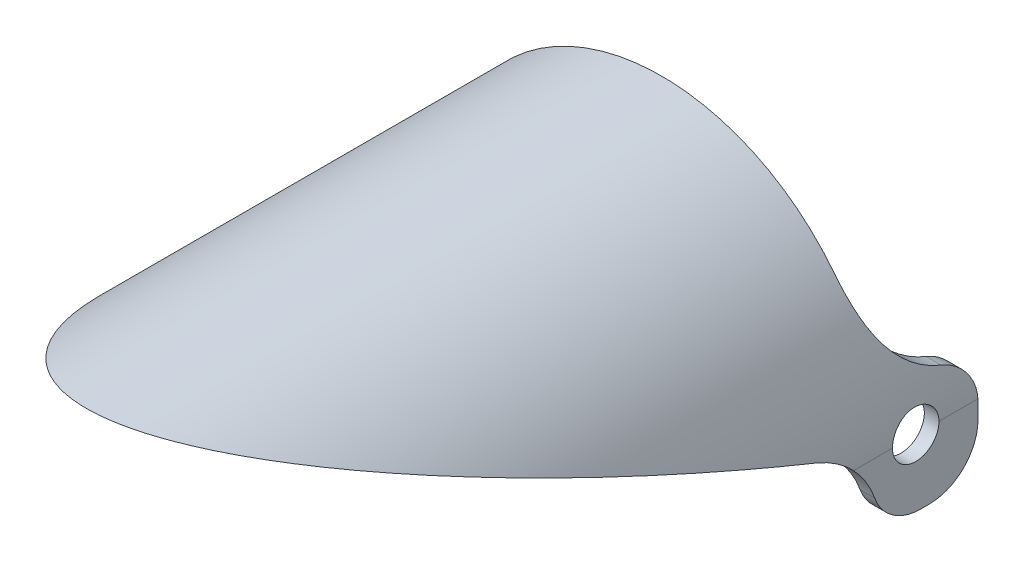
SolidWorks part; units mm, degrees
ref_plane "Front Plane" through (0, 0, 0) normal (0, 0, 1) x (1, 0, 0)
ref_plane "Top Plane" through (0, 0, 0) normal (0, 1, 0) x (1, 0, 0)
ref_plane "Right Plane" through (0, 0, 0) normal (1, 0, 0) x (0, 0, -1)
sketch "Sketch2" plane through (0, 0, 0) normal (0, 0, 1) x (1, 0, 0)
  line L0 (-44.875, 0) -> (-44.875, -13.7113)
  line L1 (-44.875, -13.7113) -> (-41.875, -13.7113)
  line L2 (44.875, -13.7113) -> (44.875, 0)
  line L3 (-41.875, 0) -> (-41.875, -13.7113)
  line L4 (41.875, 0) -> (41.875, -13.7113)
  line L5 (41.875, -13.7113) -> (44.875, -13.7113)
  arc A0 (44.875, 0) -> (-44.875, 0) centre (0, 0) ccw
  arc A1 (41.875, 0) -> (-41.875, 0) centre (0, 0) ccw
  circle A3 centre (0, 0) radius 41.875 construction
  circle A4 centre (0, 0) radius 44.875 construction
  point P4 (42.9142, 13.1202)
  point P13 (41.875, 0)
  dimension "D1" = 89.75
  dimension "D2" = 3
extrude "Boss-Extrude1" add sketch "Sketch2" along normal blind 138
sketch "Sketch3" plane through (0, 0, 0) normal (1, 0, 0) x (0, 0, -1)
  line L0 (-20, 44.875) -> (-20, 7.7299)
  line L1 (0, 44.875) -> (-138, 44.875) construction
  line L2 (-20, 7.7299) -> (0, 7.7299)
  line L3 (0, 0) -> (0, 44.875) construction
  line L4 (0, 7.7299) -> (0, -13.7113)
  line L5 (0, -13.7113) -> (-20, -13.7113)
  line L7 (-138, -13.7113) -> (0, -13.7113) construction
  line L8 (-20, -13.7113) -> (-20, 0)
  line L10 (-138, 0) -> (0, 0) construction
  line L11 (-138, 44.875) -> (-20, 44.875)
  line L12 (-20, 0) -> (-138, 44.875)
  dimension "D1" = 20
extrude "Cut-Extrude1" cut sketch "Sketch3" against normal blind 138 and the other way blind 138 flip side to cut
fillet "Fillet1" radius 20 4 edges at (-43.375, 0, 20) (43.375, 0, 20) (-42.6798, 7.7299, 20) (42.6798, 7.7299, 20)
fillet "Fillet2" radius 10 6 edges at (-43.375, -13.7113, 20) (43.375, -13.7113, 20) (43.375, -13.7113, 0) (-43.375, -13.7113, 0) (42.6798, 7.7299, 0) (-42.6798, 7.7299, 0)
sketch "Sketch4" plane through (0, 0, 0) normal (1, 0, 0) x (0, 0, -1)
  line L0 (-25.5156, 0) -> (-0.0154, 0) construction
  circle A0 centre (-12.7655, 0) radius 4.765
  dimension "D1" = 9.53
extrude "Cut-Extrude2" cut sketch "Sketch4" against normal through all and the other way through all
